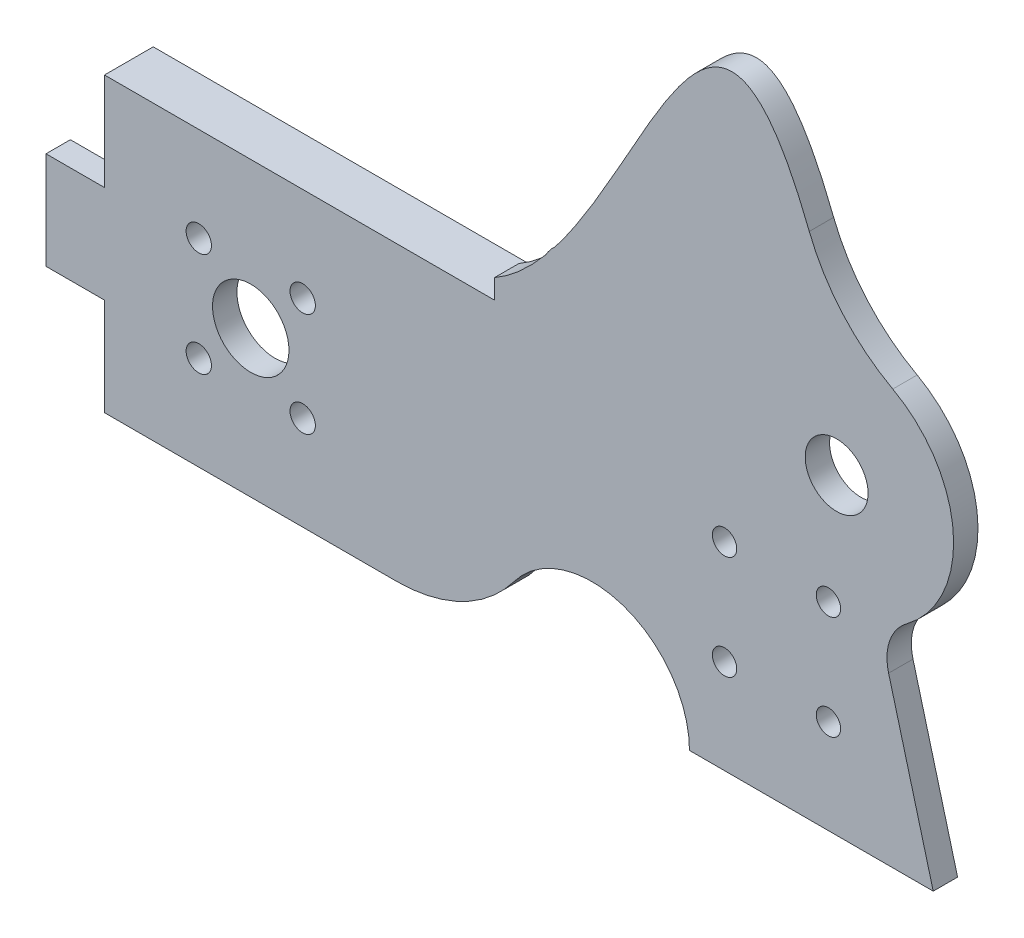
SolidWorks part; units mm, degrees
ref_plane "Front Plane" through (0, 0, 0) normal (0, 0, 1) x (1, 0, 0)
ref_plane "Top Plane" through (0, 0, 0) normal (0, 1, 0) x (1, 0, 0)
ref_plane "Right Plane" through (0, 0, 0) normal (1, 0, 0) x (0, 0, -1)
sketch "Sketch1" plane through (0, 0, 0) normal (0, 0, 1) x (1, 0, 0)
  line L0 (0, 0) -> (107.95, 0)
  line L3 (0, 38.1) -> (0, 25.4)
  line L4 (95.3675, 55.88) -> (0, 38.1)
  line L5 (0, 19.05) -> (100.2273, 19.05) construction
  line L6 (19.05, 19.05) -> (19.05, 28.62) construction
  line L7 (19.05, 19.05) -> (25.817, 25.817) construction
  line L8 (107.95, 0) -> (100.9363, 26.1756)
  line L10 (0, 12.7) -> (0, 0)
  line L11 (0, 25.4) -> (-7.62, 25.4)
  line L13 (0, 12.7) -> (-7.62, 12.7)
  line L14 (-7.62, 25.4) -> (-7.62, 12.7)
  line L15 (100.9363, 26.1756) -> (100.8688, 26.4276)
  arc A0 (100.8688, 26.4276) -> (95.3675, 55.88) centre (95.3675, 40.64) ccw
  circle A1 centre (95.3675, 40.64) radius 4.0957
  circle A2 centre (19.05, 19.05) radius 9.57 construction
  circle A3 centre (25.817, 25.817) radius 1.651
  circle A4 centre (25.817, 12.283) radius 1.651
  circle A5 centre (12.283, 12.283) radius 1.651
  circle A6 centre (12.283, 25.817) radius 1.651
  point P26 (19.05, 19.05)
  dimension "D1" = 8.1915
  dimension "D5" = 15.24
  dimension "D4" = 19.14
  dimension "D7" = 3.302
  dimension "D11" = 97.0107
  dimension "D2" = 38.1
  dimension "D3" = 40.64
  dimension "D6" = 107.95
  dimension "D8" = 45
  dimension "D9" = 4
  dimension "D10" = 19.05
  dimension "D12" = 75
  dimension "D14" = 12.7
  dimension "D15" = 12.7
  dimension "D16" = 7.62
extrude "Boss-Extrude1" add sketch "Sketch1" along normal blind 3.175
sketch "Sketch2" plane through (0, 0, 3.175) normal (0, 0, 1) x (1, 0, 0)
  circle A0 centre (95.3675, 40.64) radius 38.1 construction
sketch "Sketch6" plane through (0, 0, 3.175) normal (0, 0, 1) x (1, 0, 0)
  line L0 (0, 0) -> (107.95, 0) construction
  line L1 (50.8, 0) -> (76.2, 0)
  arc A0 (76.2, 0) -> (50.8, 0) centre (63.5, 0) ccw
  dimension "D1" = 25.4
  dimension "D2" = 31.75
extrude "Cut-Extrude2" cut sketch "Sketch6" against normal blind 6.35
sketch "Sketch7" plane through (0, 0, 3.175) normal (0, 0, 1) x (1, 0, 0)
  line L0 (12.283, 25.817) -> (25.817, 12.283) construction
  line L1 (12.283, 12.283) -> (25.817, 25.817) construction
  line L2 (12.283, 25.817) -> (78.4839, 25.817) construction
  line L3 (11.7326, 12.283) -> (12.283, 12.283) construction
  circle A0 centre (19.05, 19.05) radius 4.9784
  circle A4 centre (80.7666, 12.283) radius 1.5875
  circle A5 centre (94.2997, 12.283) radius 1.5875
  circle A6 centre (80.7666, 25.817) radius 1.5875
  circle A7 centre (94.2997, 25.817) radius 1.5875
  point P19 (91.5741, 12.283)
  point P24 (94.2997, 25.817)
  point P25 (80.7666, 25.817)
  dimension "D1" = 9.9568
  dimension "D2" = 3.175
  dimension "D3" = 13.5331
extrude "Cut-Extrude3" cut sketch "Sketch7" against normal through all
fillet "Fillet1" radius 6.35 1 edges at (100.8688, 26.4276, 1.5875)
sketch "Sketch8" plane through (0, 0, 3.175) normal (0, 0, 1) x (1, 0, 0)
  line L1 (0, 38.1) -> (50.8, 38.1)
  line L2 (0, 38.1) -> (0, 50.8)
  line L3 (0, 50.8) -> (50.8, 50.8)
  line L4 (50.8, 38.1) -> (50.8, 50.8)
  dimension "D1" = 50.8
  dimension "D2" = 12.7
extrude "Cut-Extrude4" cut sketch "Sketch8" against normal blind 50.8
sketch "Sketch9" plane through (0, 0, 3.175) normal (0, 0, 1) x (1, 0, 0)
  line L3 (50.8, 40.64) -> (57.15, 40.64)
  line L5 (57.15, 40.64) -> (50.8, 40.64)
  line L6 (57.15, 40.64) -> (57.15, 50.8)
  line L7 (57.15, 50.8) -> (50.8, 50.8)
  line L8 (50.8, 40.64) -> (50.8, 50.8)
  line L9 (0, 38.1) -> (50.8, 38.1) construction
  line M8 (50.8, 47.571) -> (50.8, 38.1)
  line M21 (95.3675, 55.88) -> (50.8, 47.571)
  dimension "D1" = 10.16
  dimension "D2" = 2.54
  dimension "D3" = 6.35
extrude "Cut-Extrude5" cut sketch "Sketch9" against normal blind 19.304 contours L3 L6 M21 M8 region at (54.0583, 44.4092, 3.175)
fillet "Fillet6" radius 6.35 1 edges at (57.15, 40.64, 1.5875)
fillet "Fillet7" radius 6.35 1 edges at (57.15, 48.7549, 1.5875)
fillet "Fillet8" radius 19.05 1 edges at (50.8, 0, 1.5875)
sketch "Sketch12" plane through (0, 0, 3.175) normal (0, 0, 1) x (1, 0, 0)
  line L0 (107.95, 0) -> (146.812, 0) construction
  line L1 (8.0257, 45.4128) -> (80.6683, 75.7903) construction
  line L2 (95.3675, 40.64) -> (80.6683, 75.7903) construction
  line L3 (80.6683, 75.7903) -> (79.4434, 78.7195) construction
  line L4 (50.8, 40.64) -> (85.0271, 40.64)
  line L5 (85.0271, 40.64) -> (95.3675, 55.88)
  arc A0 (61.8128, 49.6242) -> (56.8883, 45.1859) centre (62.9766, 43.3817) ccw construction
  circle A1 centre (19.05, 19.05) radius 28.575 construction
  circle A2 centre (95.3675, 40.64) radius 38.1 construction
  circle A3 centre (80.6683, 75.7903) radius 3.175 construction
  spline S0 degree 3 poles (50.8, 40.64) (70.7778, 52.1788) (78.5943, 111.5434) (95.3675, 55.88) knots 0 0 0 0 1 1 1 1
  dimension "D2" = 6.35
  dimension "D1" = 38.862
extrude "Boss-Extrude2" add sketch "Sketch12" against normal blind 3.175
fillet "Fillet9" radius 24.13 1 edges at (95.3675, 55.88, 1.5875)
sketch "Sketch13" plane through (0, 0, 0) normal (0, 0, -1) x (-1, 0, 0)
  line L0 (0, 38.1) -> (0, 25.4) construction
  line L1 (-50.8, 38.1) -> (0, 38.1)
  line L2 (-50.8, 38.1) -> (-50.8, 28.4023)
  line L3 (-50.8, 28.4023) -> (0, 28.4023)
  line L4 (0, 38.1) -> (0, 28.4023)
  line L5 (0, 12.7) -> (0, 0) construction
  line L6 (0, 8.5046) -> (-38.1, 8.5046)
  line L7 (0, 8.5046) -> (0, 0)
  line L8 (0, 0) -> (-38.1, 0)
  line L9 (-38.1, 8.5046) -> (-38.1, 0)
extrude "Boss-Extrude3" add sketch "Sketch13" along normal blind 3.175
